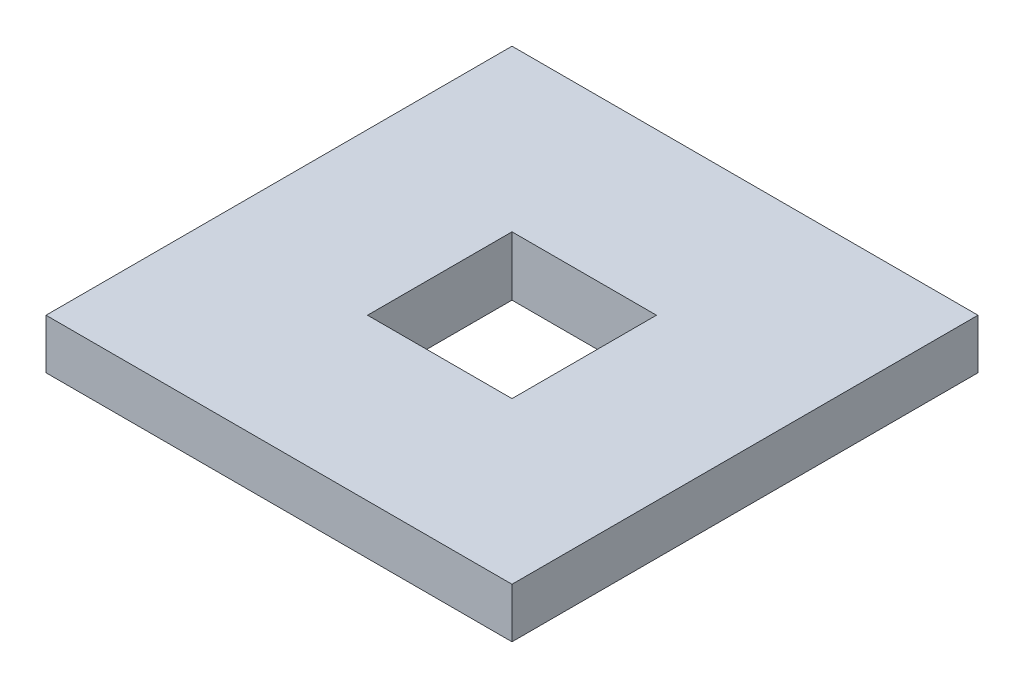
SolidWorks part; units mm, degrees
ref_plane "Front Plane" through (0, 0, 0) normal (0, 0, 1) x (1, 0, 0)
ref_plane "Top Plane" through (0, 0, 0) normal (0, 1, 0) x (1, 0, 0)
ref_plane "Right Plane" through (0, 0, 0) normal (1, 0, 0) x (0, 0, -1)
sketch "Sketch1" plane through (0, 0, 0) normal (0, 1, 0) x (1, 0, 0)
  line L0 (12.5, 16.375) -> (12.5, 25) construction
  line L1 (0, 0) -> (25, 0)
  line L2 (0, 0) -> (0, 25)
  line L3 (0, 25) -> (25, 25)
  line L4 (25, 0) -> (25, 25)
  line L5 (8.625, 16.375) -> (16.375, 16.375)
  line L6 (8.625, 16.375) -> (8.625, 8.625)
  line L7 (8.625, 8.625) -> (16.375, 8.625)
  line L8 (16.375, 16.375) -> (16.375, 8.625)
  line L9 (16.375, 12.5) -> (25, 12.5) construction
  dimension "D1" = 25
  dimension "D2" = 7.75
extrude "Boss-Extrude1" add sketch "Sketch1" along normal blind 3.175
sketch "Sketch4" plane through (0, 0, 0) normal (0, -1, 0) x (1, 0, 0)
  line L12 (25, -25) -> (0, -25) construction
  line L13 (25, 0) -> (25, -25) construction
  line L14 (0, -25) -> (0, 0) construction
  line L15 (0, 0) -> (25, 0) construction
  line L16 (25, -25) -> (0, -25)
  line L17 (25, 0) -> (25, -25)
  line L18 (0, -25) -> (0, 0)
  line L19 (0, 0) -> (25, 0)
  line L21 (5.175, -2) -> (19.825, -2)
  line L22 (2, -5.175) -> (2, -19.825)
  line L23 (5.175, -23) -> (19.825, -23)
  line L24 (23, -5.175) -> (23, -19.825)
  arc A0 (2, -5.175) -> (5.175, -2) centre (5.175, -5.175) cw
  arc A1 (19.825, -23) -> (23, -19.825) centre (19.825, -19.825) ccw
  arc A2 (5.175, -23) -> (2, -19.825) centre (5.175, -19.825) cw
  arc A3 (23, -5.175) -> (19.825, -2) centre (19.825, -5.175) ccw
  point P2 (25.5, -25.5)
  point P9 (22.7376, -1.3626)
  point P10 (0.5222, -1.9513)
  point P11 (36.9957, -19.0128)
  point P12 (25.5, -25.5)
  point P13 (23.8596, -0.5)
  dimension "D1" = 2
  dimension "D2" = 2
  dimension "D3" = 2
  dimension "D4" = 3.175
  dimension "D5" = 3.175
extrude "Cut-Extrude1" cut sketch "Sketch4" against normal blind 0.5
